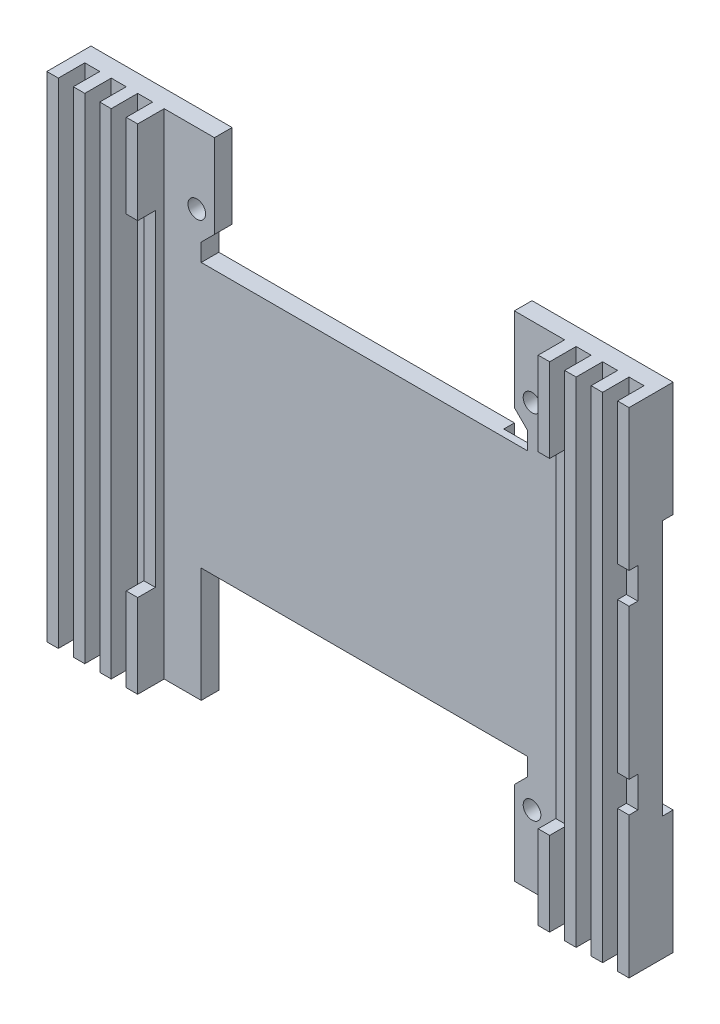
SolidWorks part; units mm, degrees
ref_plane "前视基准面" through (0, 0, 0) normal (0, 0, 1) x (1, 0, 0)
ref_plane "上视基准面" through (0, 0, 0) normal (0, 1, 0) x (1, 0, 0)
ref_plane "右视基准面" through (0, 0, 0) normal (1, 0, 0) x (0, 0, -1)
other "Configuration Table"
sketch "草图1" plane through (0, 0, 0) normal (0, 0, 1) x (1, 0, 0)
  line L0 (-18.5, 15) -> (18.5, 15)
  line L1 (18.5, 15) -> (18.5, 17)
  line L2 (18.5, 17) -> (17, 18.5)
  line L3 (17, 18.5) -> (17, 28)
  line L4 (17, 28) -> (33, 28)
  line L5 (33, 28) -> (33, -28)
  line L6 (33, -28) -> (17, -28)
  line L7 (17, -28) -> (17, -18.5)
  line L8 (17, -18.5) -> (18.5, -17)
  line L9 (18.5, -17) -> (18.5, -15)
  line L10 (18.5, -15) -> (-18.5, -15)
  line L11 (-18.5, -15) -> (-18.5, -17)
  line L12 (-18.5, -17) -> (-17, -18.5)
  line L13 (-17, -18.5) -> (-17, -28)
  line L14 (-17, -28) -> (-33, -28)
  line L15 (-33, -28) -> (-33, 28)
  line L16 (-33, 28) -> (-17, 28)
  line L17 (-17, 28) -> (-17, 18.5)
  line L18 (-17, 18.5) -> (-18.5, 17)
  line L19 (-18.5, 17) -> (-18.5, 15)
  line L20 (-34.3599, 0) -> (-7.4221, 0) construction
  line L21 (0, 36.2606) -> (0, 17.316) construction
  line L22 (-18.5, -17) -> (-18.5, -28)
  circle A0 centre (-19, 20) radius 1
  circle A1 centre (19, 20) radius 1
  circle A2 centre (19, -20) radius 1
  dimension "D9" = 2
  dimension "D1" = 30
  dimension "D2" = 40
  dimension "D3" = 66
  dimension "D4" = 38
  dimension "D5" = 37
  dimension "D6" = 34
  dimension "D7" = 28
  dimension "D8" = 2
extrude "凸台-拉伸1" add sketch "草图1" along normal blind 2 contours L22 L11 L10 L9 L8 L7 L6 L5 L4 L3 L2 L1 L0 L19 L18 L17 L16 L15 L14 A2 A1 A0 region at (0.0771, 0.1042, 0)
sketch "草图2" plane through (0, 0, 2) normal (0, 0, 1) x (1, 0, 0)
  line L1 (-33, -28) -> (-31.7, -28)
  line L2 (-33, -28) -> (-33, 28)
  line L3 (-33, 28) -> (-31.7, 28)
  line L4 (-31.7, -28) -> (-31.7, 28)
  line L6 (33, -28) -> (31.7, -28)
  line L7 (33, -28) -> (33, 28)
  line L8 (33, 28) -> (31.7, 28)
  line L9 (31.7, -28) -> (31.7, 28)
  line L10 (-30, -28) -> (-28.7, -28)
  line L11 (-30, -28) -> (-30, 28)
  line L12 (-30, 28) -> (-28.7, 28)
  line L13 (-28.7, -28) -> (-28.7, 28)
  line L14 (-27, -28) -> (-25.7, -28)
  line L15 (-27, -28) -> (-27, 28)
  line L16 (-27, 28) -> (-25.7, 28)
  line L17 (-25.7, -28) -> (-25.7, 28)
  line L18 (-24, -28) -> (-22.7, -28)
  line L19 (-24, -28) -> (-24, 28)
  line L20 (-24, 28) -> (-22.7, 28)
  line L21 (-22.7, -28) -> (-22.7, 28)
  line L22 (-33, -28) -> (-30, -28) construction
  line L23 (30, -28) -> (28.7, -28)
  line L24 (30, -28) -> (30, 28)
  line L25 (30, 28) -> (28.7, 28)
  line L26 (28.7, -28) -> (28.7, 28)
  line L27 (27, -28) -> (25.7, -28)
  line L28 (27, -28) -> (27, 28)
  line L29 (27, 28) -> (25.7, 28)
  line L30 (25.7, -28) -> (25.7, 28)
  line L31 (24, -28) -> (22.7, -28)
  line L32 (24, -28) -> (24, 28)
  line L33 (24, 28) -> (22.7, 28)
  line L34 (22.7, -28) -> (22.7, 28)
  line L35 (33, -28) -> (30, -28) construction
  dimension "D1" = 1.3
  dimension "D2" = 1.3
  dimension "D4" = 3
  dimension "D6" = 3
  dimension "D3" = 4
  dimension "D5" = 4
extrude "凸台-拉伸2" add sketch "草图2" along normal blind 3
sketch "草图3" plane through (0, 0, 0) normal (0, 0, -1) x (-1, 0, 0)
  line L0 (0, 21.7958) -> (0, 32.5445) construction
  line L1 (-10, -3) -> (10, -3)
  line L2 (-10, -3) -> (-10, 11)
  line L3 (-10, 11) -> (10, 11)
  line L4 (10, -3) -> (10, 11)
  line L5 (18.5, 15) -> (-18.5, 15) construction
  line L6 (-33, 28) -> (-33, -28) construction
  line L7 (-15, 15) -> (-33, 15)
  line L8 (-15, 15) -> (-15, -3)
  line L9 (-15, -3) -> (-33, -3)
  line L10 (-33, 15) -> (-33, -3)
  line L12 (-33, -3) -> (-23, -3)
  line L13 (-33, -3) -> (-33, -14)
  line L14 (-33, -14) -> (-23, -14)
  line L15 (-23, -3) -> (-23, -14)
  line M16 (18.5, 15) -> (-18.5, 15)
  line M21 (-33, 28) -> (-33, -28)
  dimension "D1" = 20
  dimension "D2" = 14
  dimension "D3" = 4
  dimension "D4" = 18
  dimension "D5" = 18
  dimension "D6" = 11
  dimension "D7" = 10
extrude "切除-拉伸1" cut sketch "草图3" against normal blind 1.2 contours L9 L8 L7 M16 M21 | L15 L9 L14 M21 | L1 L0 L3 L2 | L0 L1 L4 L3 region at (0, 4, 0) region at (24, 6, 0) region at (28, -8.5, 0)
sketch "草图6" plane through (0, 0, 0) normal (0, 0, -1) x (-1, 0, 0)
  line L1 (29.5, -28) -> (25, -28)
  line L2 (29.5, -28) -> (29.5, -20)
  line L3 (29.5, -20) -> (25, -20)
  line L4 (25, -28) -> (25, -20)
  line L5 (33, -28) -> (33, 28) construction
  line L6 (18.5, -28) -> (33, -28) construction
  point P4 (27.25, -28)
  dimension "D2" = 8
  dimension "D3" = 3.5
  dimension "D4" = 4.5
extrude "切除-拉伸4" cut sketch "草图6" against normal blind 1.2
sketch "草图4" plane through (0, 0, 5) normal (0, 0, 1) x (1, 0, 0)
  line L0 (31.7, 28) -> (31.7, -28) construction
  line L1 (31.7, -12) -> (33, -12)
  line L2 (31.7, -12) -> (31.7, -8.5)
  line L3 (31.7, -8.5) -> (33, -8.5)
  line L4 (33, -12) -> (33, -8.5)
  line L5 (33, -28) -> (33, 28) construction
  line L6 (31.7, -28) -> (33, -28) construction
  line L7 (31.7, 28) -> (31.7, -28) construction
  line L8 (31.7, 8.5) -> (33, 8.5)
  line L9 (31.7, 8.5) -> (31.7, 12)
  line L10 (31.7, 12) -> (33, 12)
  line L11 (33, 8.5) -> (33, 12)
  line L12 (33, 28) -> (31.7, 28) construction
  dimension "D1" = 16
  dimension "D2" = 3.5
  dimension "D3" = 3.5
  dimension "D4" = 16
extrude "切除-拉伸2" cut sketch "草图4" against normal blind 1
sketch "草图5" plane through (0, 0, 5) normal (0, 0, 1) x (1, 0, 0)
  line L0 (24, -28) -> (24, 28) construction
  line L1 (24, 18.5) -> (-24, 18.5)
  line L2 (24, 18.5) -> (24, -18.5)
  line L3 (24, -18.5) -> (-24, -18.5)
  line L4 (-24, 18.5) -> (-24, -18.5)
  line L5 (-24, 28) -> (-24, -28) construction
  line L6 (-1000, 0) -> (49000, 0) construction
  dimension "D1" = 37
extrude "切除-拉伸3" cut sketch "草图5" against normal blind 2
